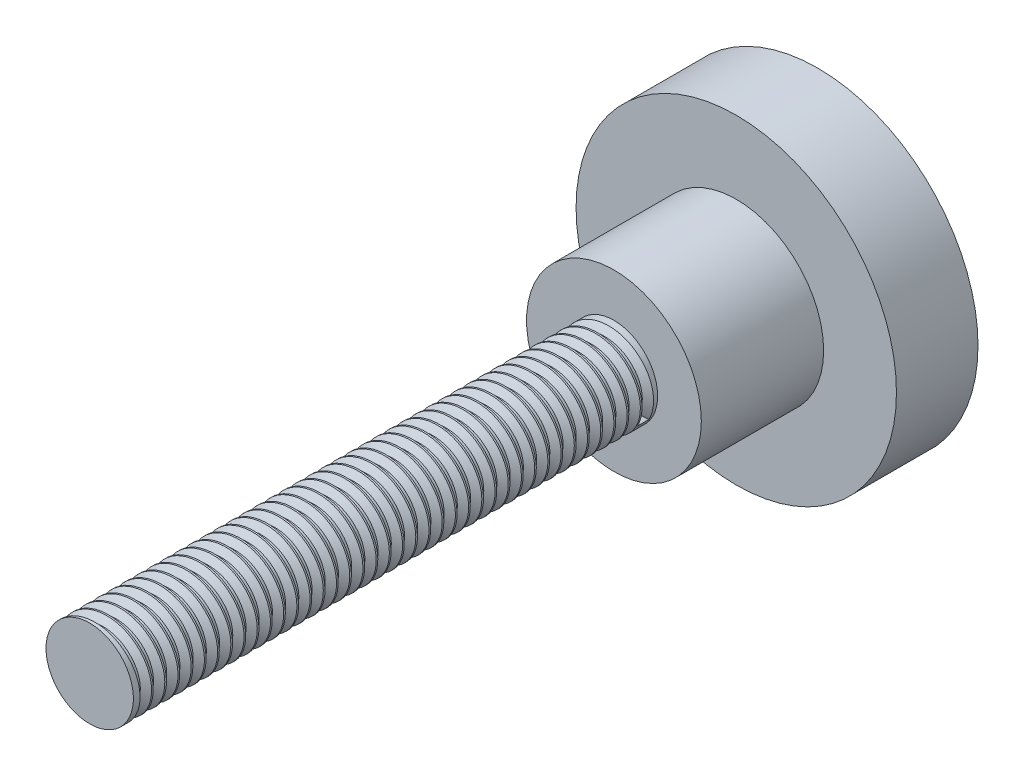
SolidWorks part; units mm, degrees
ref_plane "前视基准面" through (0, 0, 0) normal (0, 0, 1) x (1, 0, 0)
ref_plane "上视基准面" through (0, 0, 0) normal (0, 1, 0) x (1, 0, 0)
ref_plane "右视基准面" through (0, 0, 0) normal (1, 0, 0) x (0, 0, -1)
sketch "草图1" plane through (0, 0, 0) normal (0, 0, 1) x (1, 0, 0)
  circle A0 centre (0, 0) radius 3
  dimension "D1" = 6
extrude "凸台-拉伸1" add sketch "草图1" along normal blind 4.2
sketch "草图2" plane through (0, 0, 4.2) normal (0, 0, 1) x (1, 0, 0)
  circle A0 centre (0, 0) radius 1.5
  dimension "D1" = 3
extrude "凸台-拉伸2" add sketch "草图2" along normal blind 18
sketch "草图3" plane through (0, 0, 0) normal (0, 0, -1) x (-1, 0, 0)
  line L1 (1.1762, -1.2714) -> (1.6892, 0.3829)
  line L2 (1.6892, 0.3829) -> (0.513, 1.6543)
  line L3 (0.513, 1.6543) -> (-1.1762, 1.2714)
  line L4 (-1.1762, 1.2714) -> (-1.6892, -0.3829)
  line L5 (-1.6892, -0.3829) -> (-0.513, -1.6543)
  line L6 (-0.513, -1.6543) -> (1.1762, -1.2714)
  circle A0 centre (0, 0) radius 1.5 construction
  dimension "D1" = 3
thread "螺纹线1" pitch 0.4536 method cut profile "螺纹线轮廓1" start angle 0, offset 0, length 17.5, pitch 0.4536, diameter 3
ref_plane "基准面4" through (-1.5, 0, 22.2) normal (0, -1, 0) x (-1, 0, 0)
sketch "螺纹线轮廓1" plane through (-1.5, 0, 22.2) normal (0, -1, 0) x (-1, 0, 0)
  line L0 (0, 0) -> (0, 0.4536) construction
  line L11 (0, 0) -> (0, 0.3969)
  line L12 (0, 0.3969) -> (-0.2455, 0.2551)
  line L13 (-0.2455, 0.2551) -> (-0.2455, 0.1417)
  line L15 (-0.2455, 0.1417) -> (0, 0)
  line L17 (-0.2455, 0.1984) -> (0, 0.1984) construction
  point P2 (0, 0)
  dimension "Pitch" = 0.4536
  dimension "Profile_Angle" = 60
  dimension "Profile_Land" = 0.1134
  dimension "Profile_Height" = 0.2455
sketch "草图4" plane through (0, 0, 0) normal (0, 0, -1) x (-1, 0, 0)
  circle A0 centre (0, 0) radius 5.5
  dimension "D1" = 11
extrude "凸台-拉伸3" add sketch "草图4" along normal blind 2.8
